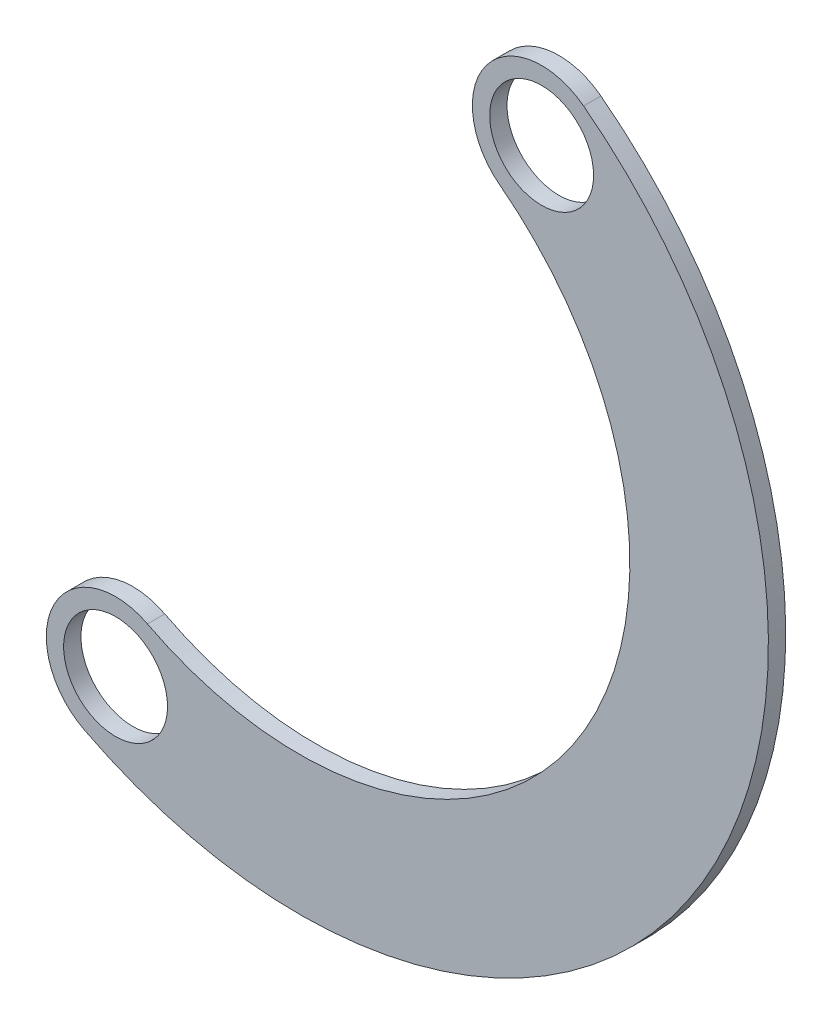
SolidWorks part; units mm, degrees
ref_plane "Front Plane" through (0, 0, 0) normal (0, 0, 1) x (1, 0, 0)
ref_plane "Top Plane" through (0, 0, 0) normal (0, 1, 0) x (1, 0, 0)
ref_plane "Right Plane" through (0, 0, 0) normal (1, 0, 0) x (0, 0, -1)
sketch "Esquisse1" plane through (0, 0, 0) normal (0, 0, 1) x (1, 0, 0)
  line L0 (-21.1361, -13.3668) -> (-19.4462, -14.4366) construction
  line L1 (-7.1443, 4.997) -> (-31.748, -33.8702) construction
  arc A0 (-31.748, -33.8702) -> (-7.1443, 4.997) centre (-21.1361, -13.3668) ccw construction
  arc A1 (-33.5866, -37.4226) -> (-4.7201, 8.1787) centre (-21.1361, -13.3668) ccw
  arc A2 (-29.9094, -30.3178) -> (-9.5685, 1.8153) centre (-21.1361, -13.3668) ccw
  arc A3 (-29.9094, -30.3178) -> (-33.5866, -37.4226) centre (-31.748, -33.8702) ccw
  arc A4 (-4.7201, 8.1787) -> (-9.5685, 1.8153) centre (-7.1443, 4.997) ccw
  circle A5 centre (-31.748, -33.8702) radius 3
  circle A6 centre (-7.1443, 4.997) radius 3
  point P3 (-1.6291, -25.7151)
  dimension "D1" = 8
  dimension "D2" = 6
  dimension "D4" = 6
  dimension "D3" = 2
base flange "Tôle de base pliée1" sketch "Esquisse1" thickness 1 reverse thickness direction no parameters "D1"=0.7366
sketch "Bend-Lines1" [suppressed] plane through (0, 0, 0) normal (0, 1, 0) x (1, 0, 0)
sketch "Bounding-Box1" [suppressed] plane through (0, 0, 0) normal (0, 1, 0) x (1, 0, 0)
sheet metal parameters "Sheet-Metal1" thickness 1 parameters "D1"=0.7366
flat pattern "Flat-Pattern1" [suppressed]
sketch "Bend-Lines2" plane through (0, 0, 0) normal (0, 1, 0) x (1, 0, 0)
sketch3d "Bounding-Box2" [suppressed]
  line L0 (13.7514, -27.0494, 0) -> (42.6338, 18.5771, 0) construction
  line L1 (-10.825, -11.492, 0) -> (18.0573, 34.1344, 0) construction
  line L2 (13.7514, -27.0494, 0) -> (-10.825, -11.492, 0) construction
  line L3 (42.6338, 18.5771, 0) -> (18.0573, 34.1344, 0) construction
